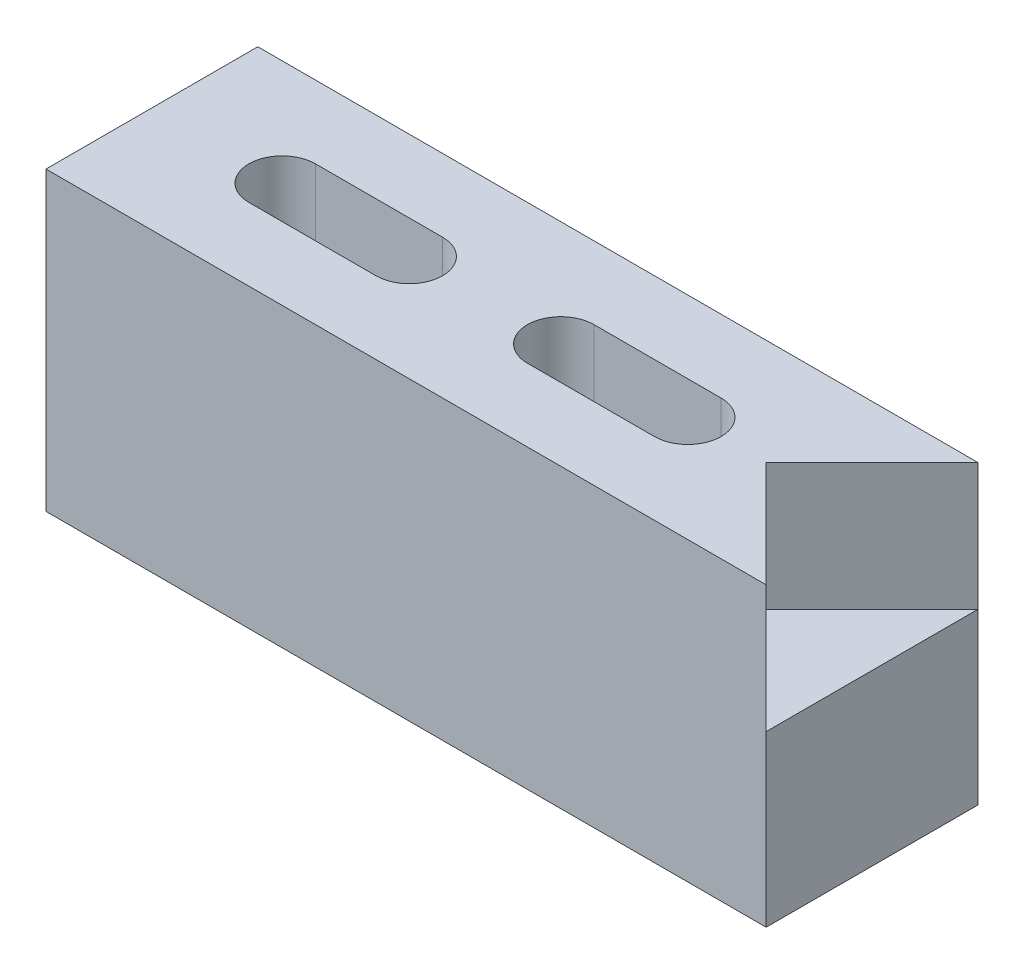
SolidWorks part; units mm, degrees
ref_plane "Front Plane" through (0, 0, 0) normal (0, 0, 1) x (1, 0, 0)
ref_plane "Top Plane" through (0, 0, 0) normal (0, 1, 0) x (1, 0, 0)
ref_plane "Right Plane" through (0, 0, 0) normal (1, 0, 0) x (0, 0, -1)
sketch "Sketch1" plane through (0, 0, 0) normal (0, 0, 1) x (1, 0, 0)
  line L0 (0, 0) -> (43.18, 0)
  line L6 (0, 0) -> (0, 17.78)
  line L10 (0, 17.78) -> (43.18, 17.78)
  line L11 (43.18, 0) -> (43.18, 17.78)
  dimension "D1" = 43.18
  dimension "D2" = 17.78
extrude "Boss-Extrude1" add sketch "Sketch1" against normal blind 12.7
sketch "Sketch3" plane through (0, 17.78, 0) normal (0, 1, 0) x (1, 0, 0)
  line L0 (43.18, 12.7) -> (36.83, 6.35)
  line L1 (36.83, 6.35) -> (43.18, 0)
  line L4 (43.18, 12.7) -> (43.18, 0)
  dimension "D2" = 90
extrude "Cut-Extrude1" cut sketch "Sketch3" against normal blind 7.62
sketch "Sketch4" plane through (0, 17.78, 0) normal (0, 1, 0) x (1, 0, 0)
  line L0 (32.131, 6.35) -> (24.511, 6.35) construction
  line L1 (32.131, 4.35) -> (24.511, 4.35)
  line L2 (32.131, 8.35) -> (24.511, 8.35)
  line L3 (15.431, 6.35) -> (7.811, 6.35) construction
  line L4 (15.431, 4.35) -> (7.811, 4.35)
  line L5 (15.431, 8.35) -> (7.811, 8.35)
  line L6 (43.18, 0) -> (0, 0) construction
  arc A0 (32.131, 4.35) -> (32.131, 8.35) centre (32.131, 6.35) ccw
  arc A1 (24.511, 8.35) -> (24.511, 4.35) centre (24.511, 6.35) ccw
  arc A2 (15.431, 4.35) -> (15.431, 8.35) centre (15.431, 6.35) ccw
  arc A3 (7.811, 8.35) -> (7.811, 4.35) centre (7.811, 6.35) ccw
  point P2 (28.321, 6.35)
  point P7 (11.621, 6.35)
  point P18 (17.431, 6.35)
  point P19 (22.511, 6.35)
  dimension "D1" = 2
  dimension "D2" = 4.699
  dimension "D3" = 7.62
  dimension "D4" = 6.35
  dimension "D5" = 5.08
extrude "Cut-Extrude2" cut sketch "Sketch4" against normal through all
